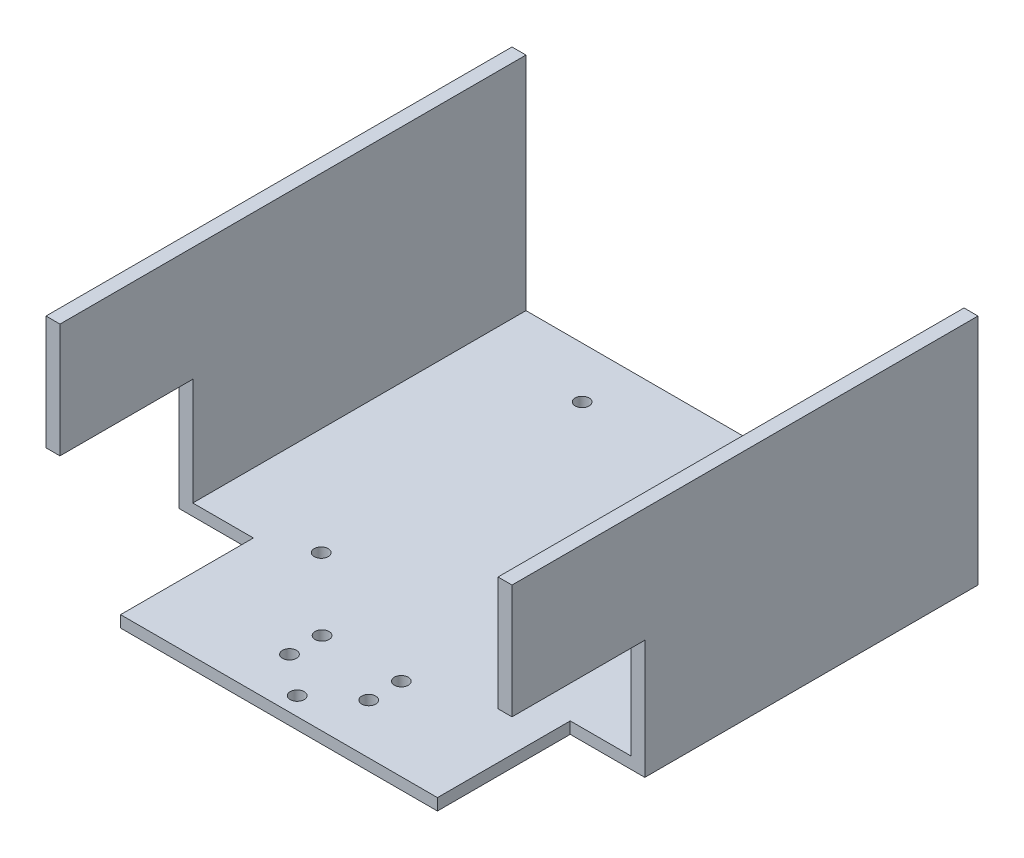
SolidWorks part; units mm, degrees
ref_plane "Alzado" through (0, 0, 0) normal (0, 0, 1) x (1, 0, 0)
ref_plane "Planta" through (0, 0, 0) normal (0, 1, 0) x (1, 0, 0)
ref_plane "Vista lateral" through (0, 0, 0) normal (1, 0, 0) x (0, 0, -1)
sketch "Croquis1" plane through (0, 0, 0) normal (0, 0, 1) x (1, 0, 0)
  line L0 (50, 0) -> (-50, 0)
  line L1 (-50, 0) -> (-50, 50)
  line L2 (-50, 50) -> (-47, 50)
  line L3 (-47, 50) -> (-47, 2.5)
  line L4 (-47, 2.5) -> (47, 2.5)
  line L5 (0, 2.5) -> (0, 0)
  line L6 (0, 0) -> (0, 13.9963) construction
  line L7 (47, 50) -> (47, 2.5)
  line L8 (50, 50) -> (47, 50)
  line L9 (50, 0) -> (50, 50)
  dimension "D1" = 50
  dimension "D2" = 50
  dimension "D3" = 3
  dimension "D4" = 2.5
extrude "Saliente-Extruir1" add sketch "Croquis1" against normal blind 100 contours L4 L7 L8 L9 L0 L1 L2 L3
sketch "Croquis2" plane through (0, 2.5, 0) normal (0, 1, 0) x (1, 0, 0)
  line L0 (0, 0) -> (0, 100) construction
  line L1 (-47, 0) -> (-34, 0)
  line L2 (-47, 0) -> (-47, 28.5)
  line L3 (-47, 28.5) -> (-34, 28.5)
  line L4 (-34, 0) -> (-34, 28.5)
  line L5 (-47, 100) -> (47, 100) construction
  line L6 (47, 28.5) -> (34, 28.5)
  line L7 (34, 0) -> (34, 28.5)
  line L8 (47, 0) -> (34, 0)
  line L9 (47, 0) -> (47, 28.5)
  dimension "D1" = 13
  dimension "D2" = 28.5
extrude "Cortar-Extruir2" cut sketch "Croquis2" against normal blind 10
ref_plane "Plano1" through (0, 2.5, 0) normal (0, 1, 0) x (1, 0, 0)
sketch "Croquis3" plane through (0, 2.5, 0) normal (0, 1, 0) x (1, 0, 0)
  line L0 (0, 0) -> (0, 100) construction
  line L1 (-47, 100) -> (47, 100) construction
  line L2 (-34, 0) -> (34, 0) construction
  circle A1 centre (0, 3.9) radius 1.5
  dimension "D1" = 3
  dimension "D2" = 3.9
extrude "Cortar-Extruir3" cut sketch "Croquis3" against normal blind 5
sketch "Croquis4" plane through (0, 2.5, 0) normal (0, 1, 0) x (1, 0, 0)
  line L0 (0, 0) -> (0, 100) construction
  line L1 (-47, 100) -> (47, 100) construction
  line L2 (0, 17.75) -> (-8.5, 17.75) construction
  line L3 (0, 10.75) -> (-8.5, 10.75) construction
  line L4 (-34, 14.25) -> (0, 14.25) construction
  line L6 (-34, 0) -> (-34, 28.5) construction
  circle A0 centre (-8.5, 17.75) radius 1.5
  circle A1 centre (-8.5, 10.75) radius 1.5
  circle A2 centre (8.5, 10.75) radius 1.5
  circle A3 centre (8.5, 17.75) radius 1.5
  dimension "D3" = 3
  dimension "D1" = 8.5
  dimension "D2" = 3.5
  dimension "D4" = 3.5
extrude "Cortar-Extruir4" cut sketch "Croquis4" against normal blind 10
sketch "Croquis5" plane through (0, 2.5, 0) normal (0, 1, 0) x (1, 0, 0)
  line L0 (-24, 100) -> (-24, 89.05) construction
  line L1 (-47, 100) -> (47, 100) construction
  line L2 (-47, 100) -> (-47, 0) construction
  line L3 (0, 100) -> (0, 0) construction
  circle A0 centre (-24, 89.05) radius 1.5
  circle A1 centre (-24, 33.05) radius 1.5
  circle A2 centre (24, 33.05) radius 1.5
  circle A3 centre (24, 89.05) radius 1.5
  dimension "D3" = 3
  dimension "D1" = 10.95
  dimension "D2" = 23
  dimension "D4" = 56
extrude "Cortar-Extruir6" cut sketch "Croquis5" against normal blind 10
sketch "Croquis6" plane through (-50, 0, 0) normal (-1, 0, 0) x (0, 0, 1)
  line L1 (0, 25.5) -> (0, 2.5)
  line L4 (-100, 0) -> (0, 0) construction
  line L6 (0, 2.5) -> (-28.5, 2.5)
  line L7 (0, 0) -> (0, 50) construction
  line L8 (-28.5, 2.5) -> (-28.5, 25.5)
  line L9 (-28.5, 25.5) -> (0, 25.5)
  dimension "D1" = 28.5
  dimension "D2" = 23
  dimension "D3" = 2.5
extrude "Cortar-Extruir8" cut sketch "Croquis6" against normal through all
sketch "Croquis7" plane through (0, 0, 0) normal (0, 0, 1) x (1, 0, 0)
  line L4 (-47, 2.5) -> (-50, 2.5)
  line L5 (-50, 2.5) -> (-50, 0)
  line L7 (-47, 0) -> (-47, 2.5)
  line L9 (-50, 2.5) -> (-50, 0)
  line L11 (-47, 0) -> (-47, 2.5)
  line L12 (50, 2.5) -> (47, 2.5)
  line L13 (47, 2.5) -> (47, 0)
  line L15 (50, 0) -> (50, 2.5)
  line L17 (47, 2.5) -> (47, 0)
  line L19 (50, 0) -> (50, 2.5)
  line L28 (-47, 2.5) -> (-50, 2.5)
  line L30 (50, 2.5) -> (47, 2.5)
  line L32 (-50, 0) -> (-47, 0)
  line L33 (-50, 0) -> (-47, 0)
  line L34 (47, 0) -> (50, 0)
  line L35 (47, 0) -> (50, 0)
  dimension "D1" = 0
  dimension "D2" = 0
extrude "Cortar-Extruir9" cut sketch "Croquis7" against normal blind 28.5
